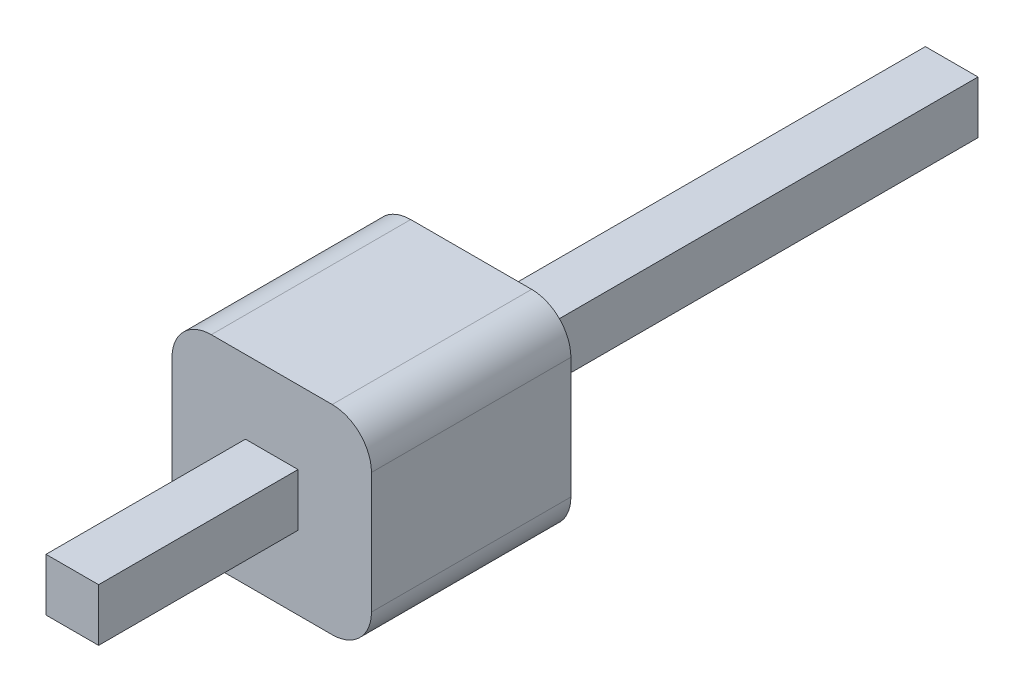
SolidWorks part; units mm, degrees
ref_plane "前视基准面" through (0, 0, 0) normal (0, 0, 1) x (1, 0, 0)
ref_plane "上视基准面" through (0, 0, 0) normal (0, 1, 0) x (1, 0, 0)
ref_plane "右视基准面" through (0, 0, 0) normal (1, 0, 0) x (0, 0, -1)
sketch "草图1" plane through (0, 0, 0) normal (0, 0, 1) x (1, 0, 0)
  line L0 (0, 5.3599) -> (0, -8.0108) construction
  line L1 (-1.27, -0.0191) -> (1.27, -0.0191)
  line L2 (-1.27, -0.0191) -> (-1.27, -2.5591)
  line L3 (-1.27, -2.5591) -> (1.27, -2.5591)
  line L4 (1.27, -0.0191) -> (1.27, -2.5591)
  dimension "D1" = 2.54
  dimension "D2" = 2.54
extrude "拉伸1" add sketch "草图1" along normal blind 2.54
ref_plane "基准面1" through (0, 0, 5.08) normal (0, 0, -1) x (-1, 0, 0)
sketch "草图2" plane through (0, 0, 5.08) normal (0, 0, -1) x (-1, 0, 0)
  line L0 (-1.27, -1.2891) -> (1.27, -1.2891) construction
  line L1 (-1.27, -2.5591) -> (-1.27, -0.0191) construction
  line L2 (1.27, -0.0191) -> (1.27, -2.5591) construction
  line L3 (0, 1.9407) -> (0, -4.2425) construction
  line L5 (-0.335, -0.9541) -> (0.335, -0.9541)
  line L6 (-0.335, -0.9541) -> (-0.335, -1.6241)
  line L7 (-0.335, -1.6241) -> (0.335, -1.6241)
  line L8 (0.335, -0.9541) -> (0.335, -1.6241)
  dimension "D1" = 0.67
  dimension "D2" = 0.67
sketch "草图3" plane through (0, 0, 0) normal (1, 0, 0) x (0, 0, -1)
  line L0 (6.12, -1.2991) -> (-5.08, -1.2991)
  line L1 (-5.08, 1.9407) -> (-5.08, -4.2425) construction
  line L8 (-2.54, -0.0191) -> (0, -0.0191) construction
  line L9 (0, -2.5591) -> (0, -0.0191) construction
  point P11 (2.54, -1.2991)
  dimension "D1" = 5.08
  dimension "D2" = 11.2
  dimension "D4" = 1.28
sweep "扫描1" add profiles "草图2" path "草图3"
fillet "圆角1" radius 0.5 4 edges at (1.27, -0.0191, 1.27) (1.27, -2.5591, 1.27) (-1.27, -2.5591, 1.27) (-1.27, -0.0191, 1.27)
